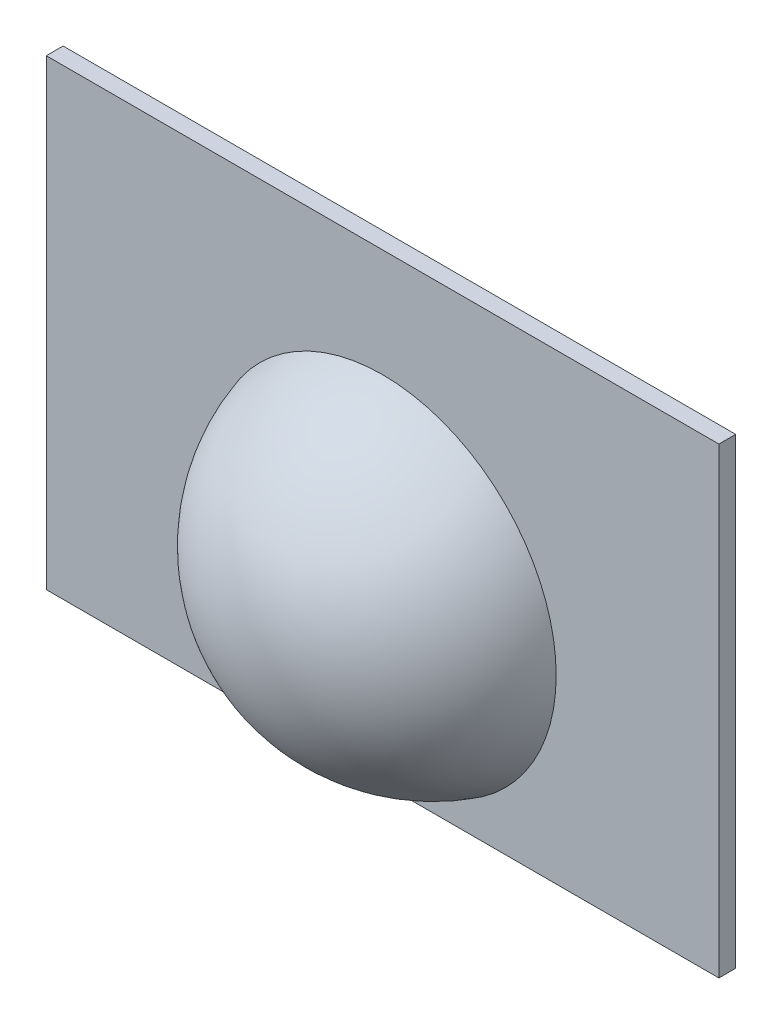
SolidWorks part; units mm, degrees
ref_plane "Front Plane" through (0, 0, 0) normal (0, 0, 1) x (1, 0, 0)
ref_plane "Top Plane" through (0, 0, 0) normal (0, 1, 0) x (1, 0, 0)
ref_plane "Right Plane" through (0, 0, 0) normal (1, 0, 0) x (0, 0, -1)
sketch "Sketch1" plane through (0, 0, 0) normal (0, 0, 1) x (1, 0, 0)
  line L0 (0, 21.5) -> (0, -21.5)
  arc A0 (0, 21.5) -> (0, -21.5) centre (0, 0) cw
  dimension "D1" = 43
revolve "Revolve1" add sketch "Sketch1" angle 360 about L0
ref_plane "Plane1" through (0, 0, 6) normal (0, 0, 1) x (1, 0, 0)
sketch "Sketch2" plane through (0, 0, 6) normal (0, 0, 1) x (1, 0, 0)
  line L0 (0, 33.5) -> (0, 0) construction
  line L1 (-40, 33.5) -> (40, 33.5)
  line L2 (-40, 33.5) -> (-40, -21.5)
  line L3 (-40, -21.5) -> (40, -21.5)
  line L4 (40, 33.5) -> (40, -21.5)
  circle A0 centre (0, 0) radius 21.5 construction
  dimension "D1" = 80
  dimension "D2" = 55
extrude "Boss-Extrude1" add sketch "Sketch2" against normal blind 2
sketch "Sketch3" plane through (0, 0, 4) normal (0, 0, 1) x (1, 0, 0)
  line L4 (-40, 33.5) -> (-40, -21.5)
  line L5 (-40, -21.5) -> (40, -21.5)
  line L6 (40, -21.5) -> (40, 33.5)
  line L7 (40, 33.5) -> (-40, 33.5)
  line L8 (-40, 33.5) -> (-40, -21.5)
  line L9 (-40, -21.5) -> (40, -21.5)
  line L10 (40, -21.5) -> (40, 33.5)
  line L11 (40, 33.5) -> (-40, 33.5)
  dimension "D1" = 0
extrude "Cut-Extrude2" cut sketch "Sketch3" against normal through all
